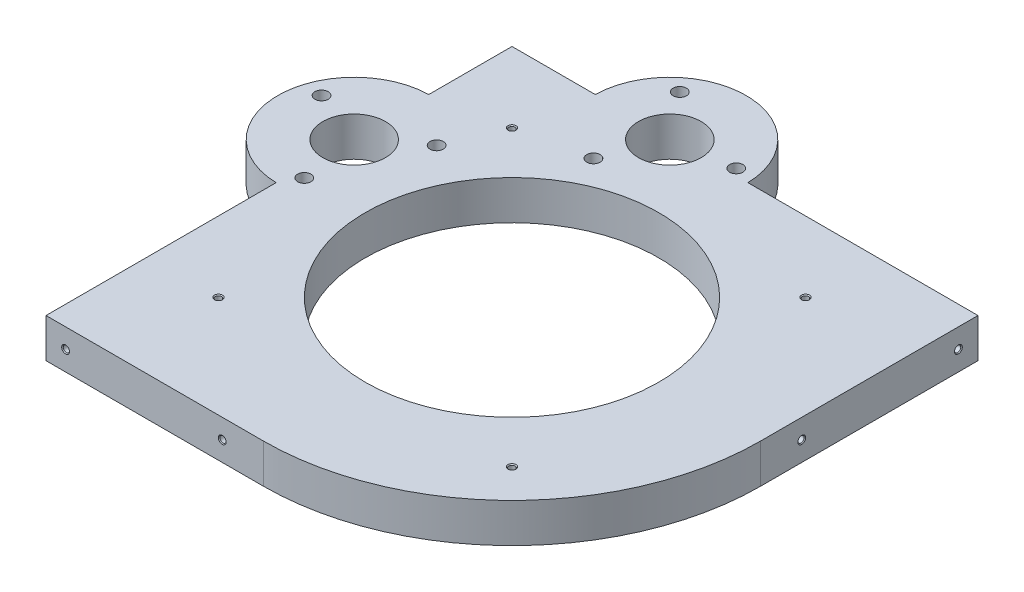
SolidWorks part; units mm, degrees
other "Markup1"
sketch "Sketch10" plane through (101, 10, 101) normal (0.4075, 0.0648, 0.9109) x (0.9078, -0.1373, -0.3964)
ref_plane "Front Plane" through (0, 0, 0) normal (0, 0, 1) x (1, 0, 0)
ref_plane "Top Plane" through (0, 0, 0) normal (0, 1, 0) x (1, 0, 0)
ref_plane "Right Plane" through (0, 0, 0) normal (1, 0, 0) x (0, 0, -1)
sketch "Sketch1" plane through (0, 0, 0) normal (0, 1, 0) x (1, 0, 0)
  line L1 (-55.5, 55.5) -> (63.5, 55.5)
  line L2 (-55.5, 55.5) -> (-55.5, -63.5)
  line L4 (88.5, 55.5) -> (88.5, 0) construction
  line L5 (63.5, 0) -> (88.5, 0) construction
  line L6 (-53, 0) -> (-55.5, 0) construction
  line L7 (0, 53) -> (0, 55.5) construction
  line L8 (0, -37.5) -> (0, -63.5) construction
  line L9 (0, -63.5) -> (-55.5, -63.5)
  line L10 (0, -63.5) -> (0, -88.5) construction
  line L11 (-55.5, -63.5) -> (-55.5, -88.5) construction
  line L12 (-55.5, -88.5) -> (0, -88.5) construction
  line L13 (63.5, 0) -> (63.5, 55.5)
  line L14 (63.5, 55.5) -> (88.5, 55.5) construction
  circle A0 centre (0, 0) radius 37.5
  circle A1 centre (0, 0) radius 53 construction
  arc A3 (0, -63.5) -> (63.5, 0) centre (0, 0) ccw
  point P18 (37.4767, -37.4767)
  point P22 (-37.4767, -37.4767)
  point P23 (-37.4767, 37.4767)
  point P24 (37.4767, 37.4767)
  point P25 (0, 0)
  point P28 (0, 0)
  dimension "D1" = 75
  dimension "D2" = 106
  dimension "D5" = 2.5
  dimension "D6" = 25
  dimension "D3" = 4
  dimension "D7" = 26
extrude "Boss-Extrude1" add sketch "Sketch1" along normal blind 10
hole_wizard "M2x0.4 Tapped Hole2" positions "Sketch4" profile "Sketch3" tap size "M2x0.4" standard "ANSI Metric" end condition through all
sketch "Sketch4" plane through (0, 10, 0) normal (0, 1, 0) x (1, 0, 0)
  point P31 (37.4767, 37.4767)
  point P33 (-37.4767, 37.4767)
  point P35 (-37.4767, -37.4767)
  point P37 (37.4767, -37.4767)
sketch "Sketch3" plane through (37.4767, 10, -37.4767) normal (1, 0, 0) x (0, 0, 1)
  line L0 (0, 0) -> (0, 10)
  line L1 (0, 10) -> (0.8, 10)
  line L2 (0.8, 10) -> (0.8, 0.225)
  line L3 (0.8, 0.225) -> (1.025, 0)
  line L5 (1.025, 0) -> (0, 0)
  line L6 (-0.8, 0.225) -> (-1.025, 0) construction
  line L11 (0, -6.35) -> (0, 107.95) construction
  dimension "Thru Tap Drill Dia." = 1.6
  dimension "Thru Tap Drill Depth" = 10
  dimension "Near C'Sink Dia." = 2.05
  dimension "Near C'Sink Angle" = 90
hole_wizard "M2x0.4 Tapped Hole1" positions "3DSketch1" profile "Sketch5" tap size "M2x0.4" standard "ANSI Metric"
sketch3d "3DSketch1"
  line L0 (-55.5, 10, 63.5) -> (-55.5, 0, 63.5) construction
  line L1 (-55.5, 10, 63.5) -> (0, 10, 63.5) construction
  line L2 (-50.5, 5, 63.5) -> (-10.5, 5, 63.5) construction
  line L4 (63.5, 10, 0) -> (63.5, 10, -55.5) construction
  line L5 (63.5, 10, -55.5) -> (63.5, 0, -55.5) construction
  line L6 (63.5, 5, -50.5) -> (63.5, 5, -10.5) construction
  point P0 (63.5, 5, -50.5)
  point P2 (63.5, 5, -10.5)
  point P4 (-50.5, 5, 63.5)
  point P6 (-10.5, 5, 63.5)
  dimension "D1" = 5
  dimension "D2" = 5
  dimension "D3" = 45
  dimension "D4" = 5
  dimension "D5" = 5
  dimension "D6" = 45
sketch "Sketch5" plane through (63.5, 5, -50.5) normal (0, 1, 0) x (0, 0, -1)
  line L0 (0, 0) -> (0, 6.4807)
  line L1 (0, 6.4807) -> (0.8, 6)
  line L2 (0.8, 6) -> (0.8, 0)
  line L5 (0.8, 0) -> (0, 0)
  line L10 (0, 6.4807) -> (-0.8, 6) construction
  line L11 (0, -6.35) -> (0, 107.95) construction
  dimension "Tap Drill Dia." = 1.6
  dimension "Tap Drill Depth" = 6
  dimension "Drill Angle" = 118
cosmetic thread "Hole Thread5" parameters "D1"=4, "D2"=2
cosmetic thread "Hole Thread6" parameters "D1"=4, "D2"=2
cosmetic thread "Hole Thread7" parameters "D1"=4, "D2"=2
cosmetic thread "Hole Thread8" parameters "D1"=4, "D2"=2
chamfer "Chamfer1" distance 0.2 angle 45 4 edges at (63.5, 5, -51.3) (63.5, 5, -11.3) (-49.7, 5, 63.5) (-9.7, 5, 63.5)
sketch "Sketch11" plane through (0, 10, 0) normal (0, 1, 0) x (1, 0, 0)
  line L0 (-55.5, 55.5) -> (0, 0) construction
  line L1 (-14.7527, 55.0578) -> (0, 0) construction
  circle A0 centre (-14.7527, 55.0578) radius 8 construction
  circle A1 centre (-14.7527, 55.0578) radius 19.5
  circle A2 centre (-55.0578, 14.7527) radius 19.5
  circle A3 centre (-55.0578, 14.7527) radius 8 construction
  circle A4 centre (0, 0) radius 37.5 construction
  dimension "D2" = 16
  dimension "D1" = 57
  dimension "D4" = 30
extrude "Boss-Extrude2" add sketch "Sketch11" against normal through all
sketch "Sketch12" plane through (0, 10, 0) normal (0, 1, 0) x (1, 0, 0)
  circle A0 centre (-14.7527, 55.0578) radius 8
  circle A1 centre (-55.0578, 14.7527) radius 8
  dimension "D1" = 16
  dimension "D2" = 16
extrude "Cut-Extrude1" cut sketch "Sketch12" against normal through all
hole_wizard "M3 Clearance Hole1" positions "Sketch13" profile "Sketch14" hole size "M3" standard "ANSI Metric" end condition through all
sketch "Sketch13" plane through (1225.1292, 0, -788.1794) normal (0, -1, 0) x (0.1231, 0, 0.9924)
  point P0 (602.6322, 1378.8069)
  point P3 (624.8952, 1365.4144)
  point P6 (602.1654, 1352.8303)
  point P9 (587.9855, 1327.9877)
  point P12 (574.5929, 1305.7248)
  point P15 (562.0089, 1328.4545)
sketch "Sketch14" plane through (-68.9756, 0, -20.3468) normal (1, 0, 0) x (0, 0, -1)
  line L0 (0, 0) -> (0, 10)
  line L1 (0, 10) -> (1.7, 10)
  line L2 (1.7, 10) -> (1.7, 0)
  line L3 (1.7, 0) -> (0, 0)
  line L4 (0, -6.35) -> (0, 107.95) construction
  dimension "Thru Hole Dia." = 3.4
  dimension "Thru Hole Depth" = 10
